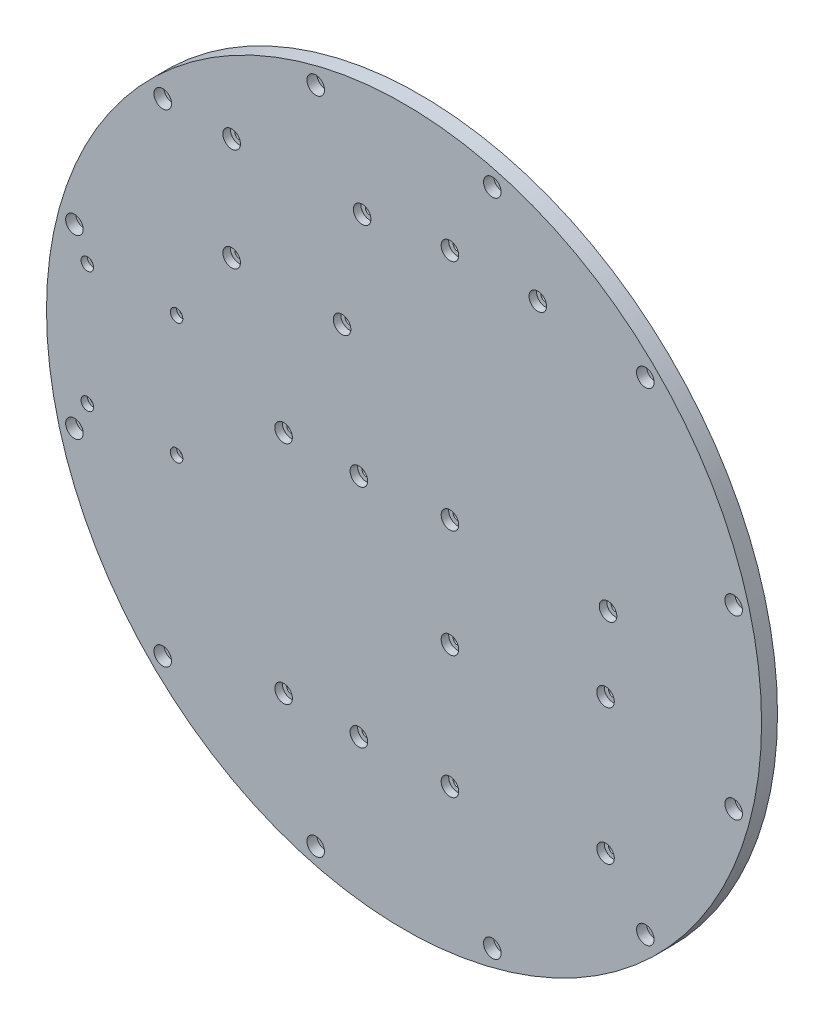
SolidWorks part; units mm, degrees
ref_plane "Plan de face" through (0, 0, 0) normal (0, 0, 1) x (1, 0, 0)
ref_plane "Plan de dessus" through (0, 0, 0) normal (0, 1, 0) x (1, 0, 0)
ref_plane "Plan de droite" through (0, 0, 0) normal (1, 0, 0) x (0, 0, -1)
sketch "Esquisse1" plane through (0, 0, 0) normal (0, 0, 1) x (1, 0, 0)
  line L0 (0, 0) -> (0, 136) construction
  line L1 (0, 0) -> (-35.1994, 131.3659) construction
  circle A3 centre (0, 0) radius 136 construction
  circle A14 centre (-35.1994, 131.3659) radius 1.75
  circle A41 centre (0, 0) radius 142.5
  circle A42 centre (35.1994, 131.3659) radius 1.75
  circle A43 centre (96.1665, 96.1665) radius 1.75
  circle A44 centre (131.3659, 35.1994) radius 1.75
  circle A45 centre (131.3659, -35.1994) radius 1.75
  circle A46 centre (96.1665, -96.1665) radius 1.75
  circle A47 centre (35.1994, -131.3659) radius 1.75
  circle A48 centre (-35.1994, -131.3659) radius 1.75
  circle A49 centre (-96.1665, -96.1665) radius 1.75
  circle A50 centre (-131.3659, -35.1994) radius 1.75
  circle A51 centre (-131.3659, 35.1994) radius 1.75
  circle A52 centre (-96.1665, 96.1665) radius 1.75
  point P31 (0, 0)
  point P34 (0, 0)
  point P41 (0, 0)
  dimension "D1" = 272
  dimension "D3" = 3.5
  dimension "D4" = 285
  dimension "D2" = 15
extrude "Boss.-Extru.1" add sketch "Esquisse1" along normal blind 6.35
sketch "Esquisse2" plane through (0, 0, 6.35) normal (0, 0, 1) x (1, 0, 0)
  circle A12 centre (35.1994, 131.3659) radius 3.5
  circle A13 centre (96.1665, 96.1665) radius 3.5
  circle A14 centre (131.3659, 35.1994) radius 3.5
  circle A15 centre (131.3659, -35.1994) radius 3.5
  circle A16 centre (96.1665, -96.1665) radius 3.5
  circle A17 centre (35.1994, -131.3659) radius 3.5
  circle A18 centre (-35.1994, -131.3659) radius 3.5
  circle A19 centre (-96.1665, -96.1665) radius 3.5
  circle A20 centre (-131.3659, -35.1994) radius 3.5
  circle A21 centre (-131.3659, 35.1994) radius 3.5
  circle A22 centre (-96.1665, 96.1665) radius 3.5
  circle A23 centre (-35.1994, 131.3659) radius 3.5
  point P20 (0, 0)
  point P27 (0, 0)
  dimension "D1" = 7
extrude "Enlèv. mat.-Extru.1" cut sketch "Esquisse2" against normal blind 4
sketch "Esquisse3" plane through (0, 0, 6.35) normal (0, 0, 1) x (1, 0, 0)
  line L0 (-126.2141, -24.13) -> (-126.2141, 24.13) construction
  line L1 (-126.2141, 24.13) -> (-90.6541, 24.13) construction
  line L2 (-90.6541, 24.13) -> (-90.6541, -24.13) construction
  line L3 (-90.6541, -24.13) -> (-126.2141, -24.13) construction
  circle A0 centre (0, 0) radius 128.5 construction
  circle A3 centre (-126.2141, -24.13) radius 1.25
  circle A4 centre (-126.2141, 24.13) radius 1.25
  circle A5 centre (-90.6541, 24.13) radius 1.25
  circle A6 centre (-90.6541, -24.13) radius 1.25
  dimension "D1" = 257
  dimension "D2" = 35.56
  dimension "D4" = 2.5
  dimension "D3" = 48.26
extrude "Enlèv. mat.-Extru.2" cut sketch "Esquisse3" against normal up to next
sketch "Esquisse4" plane through (0, 0, 6.35) normal (0, 0, 1) x (1, 0, 0)
  circle A0 centre (-126.2141, -24.13) radius 2.5
  circle A1 centre (-126.2141, 24.13) radius 2.5
  circle A2 centre (-90.6541, 24.13) radius 2.5
  circle A3 centre (-90.6541, -24.13) radius 2.5
  dimension "D1" = 5
extrude "Enlèv. mat.-Extru.3" cut sketch "Esquisse4" against normal blind 2.5
sketch "Esquisse5" plane through (0, 0, 6.35) normal (0, 0, 1) x (1, 0, 0)
  circle A0 centre (-48, -85) radius 1.75
  circle A1 centre (-48, 5) radius 1.75
  circle A2 centre (-18, 5) radius 1.75
  circle A3 centre (-18, -85) radius 1.75
  circle A4 centre (0, 0) radius 142.5 construction
  circle A5 centre (0, 0) radius 142.5 construction
  dimension "D4" = 3.5
  dimension "D1" = 90
  dimension "D2" = 30
  dimension "D3" = 5
  dimension "D5" = 18
extrude "Enlèv. mat.-Extru.4" cut sketch "Esquisse5" against normal up to next
sketch "Esquisse6" plane through (0, 0, 6.35) normal (0, 0, 1) x (1, 0, 0)
  circle A0 centre (-48, -85) radius 3.5
  circle A1 centre (-18, -85) radius 3.5
  circle A2 centre (-48, 5) radius 3.5
  circle A3 centre (-18, 5) radius 3.5
  dimension "D1" = 7
extrude "Enlèv. mat.-Extru.5" cut sketch "Esquisse6" against normal blind 3
sketch "Esquisse7" plane through (0, 0, 6.35) normal (0, 0, 1) x (1, 0, 0)
  circle A0 centre (-68.7, 55) radius 1.75
  circle A1 centre (-68.7, 96) radius 1.75
  circle A2 centre (-24.7, 54) radius 1.75
  circle A3 centre (-16.7, 96) radius 1.75
  circle A5 centre (-18, 5) radius 3.5 construction
  circle A7 centre (-48, 5) radius 3.5 construction
  circle A8 centre (-18, 5) radius 3.5 construction
  circle A9 centre (-48, 5) radius 3.5 construction
  dimension "D5" = 3.5
  dimension "D7" = 50
  dimension "D1" = 44
  dimension "D2" = 41
  dimension "D3" = 42
  dimension "D4" = 52
  dimension "D6" = 6.7
extrude "Enlèv. mat.-Extru.6" cut sketch "Esquisse7" against normal up to next
sketch "Esquisse8" plane through (0, 0, 6.35) normal (0, 0, 1) x (1, 0, 0)
  circle A0 centre (-68.7, 55) radius 3.5
  circle A1 centre (-68.7, 96) radius 3.5
  circle A2 centre (-24.7, 54) radius 3.5
  circle A3 centre (-16.7, 96) radius 3.5
  dimension "D1" = 7
extrude "Enlèv. mat.-Extru.7" cut sketch "Esquisse8" against normal blind 3
sketch "Esquisse9" plane through (0, 0, 6.35) normal (0, 0, -1) x (-1, 0, 0)
  circle A0 centre (-18.3, 101) radius 1.75
  circle A1 centre (-18.3, 8) radius 1.75
  circle A2 centre (-53.3, 101) radius 1.75
  circle A3 centre (-81.3, 8) radius 1.75
  circle A6 centre (16.7, 96) radius 1.75 construction
  circle A7 centre (16.7, 96) radius 1.75 construction
  point P11 (-55.7541, 102.7509)
  point P12 (-53.1229, 106)
  point P13 (-18.3, 23.1332)
  point P14 (-80.3, 13)
  dimension "D1" = 3.5
  dimension "D2" = 93
  dimension "D3" = 35
  dimension "D5" = 63
  dimension "D6" = 35
  dimension "D8" = 5
extrude "Enlèv. mat.-Extru.8" cut sketch "Esquisse9" along normal up to next
sketch "Esquisse10" plane through (0, 0, 6.35) normal (0, 0, 1) x (1, 0, 0)
  circle A0 centre (18.3, 8) radius 3.5
  circle A1 centre (18.3, 101) radius 3.5
  circle A2 centre (53.3, 101) radius 3.5
  circle A3 centre (81.3, 8) radius 3.5
  dimension "D1" = 7
extrude "Enlèv. mat.-Extru.9" cut sketch "Esquisse10" against normal blind 3
sketch "Esquisse11" plane through (0, 0, 6.35) normal (0, 0, -1) x (-1, 0, 0)
  circle A0 centre (-18.3, -35) radius 1.75
  circle A1 centre (-18.3, -84) radius 1.75
  circle A2 centre (-80.3, -22) radius 1.75
  circle A3 centre (-80.3, -76) radius 1.75
  circle A7 centre (-18.3, 8) radius 1.75 construction
  circle A8 centre (-18.3, 8) radius 1.75 construction
  dimension "D1" = 3.5
  dimension "D2" = 49
  dimension "D6" = 30
  dimension "D3" = 62
  dimension "D4" = 13
  dimension "D5" = 54
extrude "Enlèv. mat.-Extru.10" cut sketch "Esquisse11" along normal up to next
sketch "Esquisse12" plane through (0, 0, 6.35) normal (0, 0, 1) x (1, 0, 0)
  circle A0 centre (18.3, -84) radius 3.5
  circle A1 centre (18.3, -35) radius 3.5
  circle A2 centre (80.3, -22) radius 3.5
  circle A3 centre (80.3, -76) radius 3.5
  dimension "D1" = 7
extrude "Enlèv. mat.-Extru.11" cut sketch "Esquisse12" against normal blind 3
